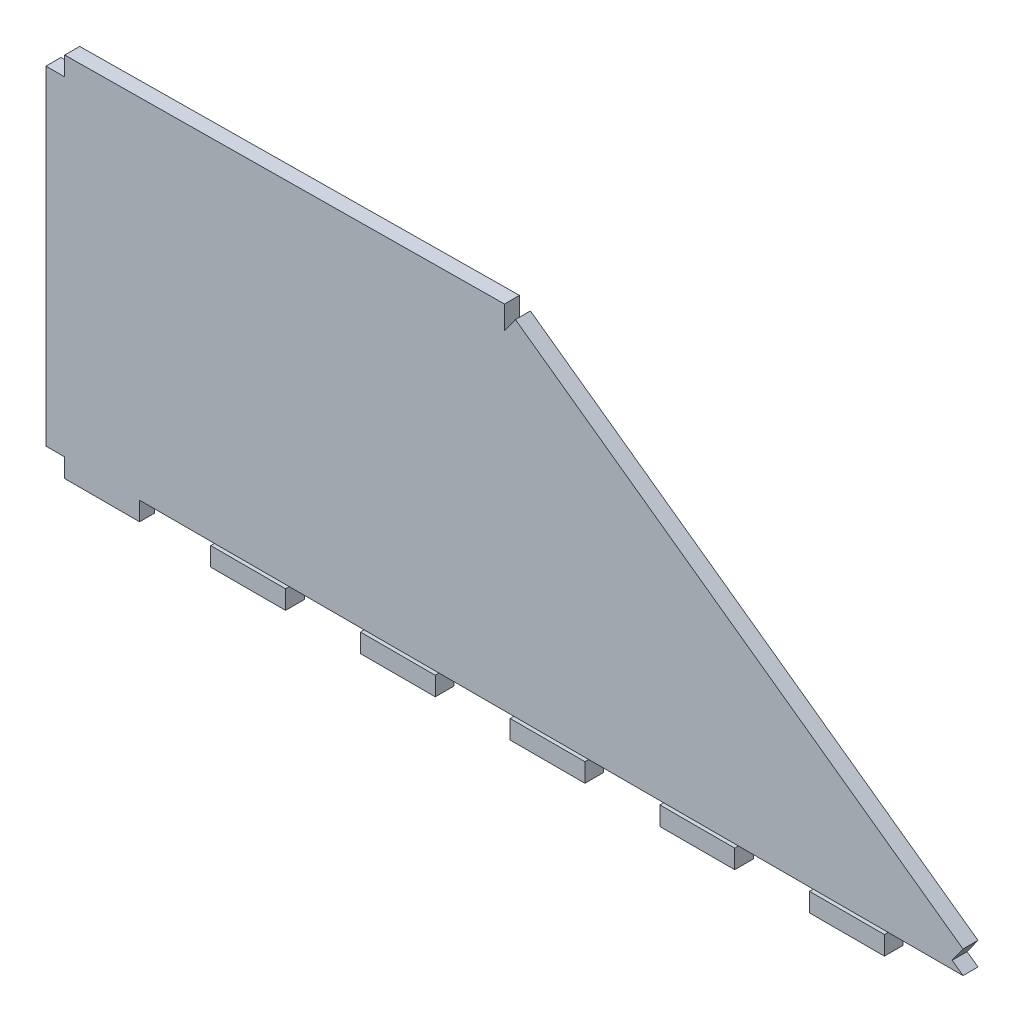
SolidWorks part; units mm, degrees
ref_plane "Front Plane" through (0, 0, 0) normal (0, 0, 1) x (1, 0, 0)
ref_plane "Top Plane" through (0, 0, 0) normal (0, 1, 0) x (1, 0, 0)
ref_plane "Right Plane" through (0, 0, 0) normal (1, 0, 0) x (0, 0, -1)
sketch "Sketch1" plane through (-5.3296, -16.203, 0) normal (0, 0, 1) x (1, 0, 0)
  line L0 (-139.4125, -47.2066) -> (-139.4125, -165.2411) construction
  line L1 (-294.9875, -47.2066) -> (-294.9875, -40.8566) construction
  line L2 (-294.9875, -47.2066) -> (-294.9875, -165.2411)
  line L3 (-294.9875, -165.2411) -> (16.1625, -165.2411) construction
  line L4 (16.1625, -158.8911) -> (16.1625, -165.2411)
  line L5 (-105.6158, -63.6519) -> (-109.3189, -68.8103) construction
  line L6 (-294.9875, -158.8911) -> (16.1625, -158.8911)
  line L7 (16.1625, -158.8911) -> (-139.4125, -47.2066)
  line L8 (-139.4125, -47.2066) -> (-294.9875, -47.2066)
  line L9 (16.1625, -158.8911) -> (16.1625, -151.0743) construction
  line L10 (-135.7094, -42.0482) -> (16.1625, -151.0743)
  line L11 (-139.4125, -47.2066) -> (-139.4125, -39.334)
  line L12 (-139.4125, -39.334) -> (-288.6375, -40.7811)
  line L13 (-288.6375, -165.2411) -> (-288.6375, -40.7811)
  line L14 (-139.4125, -47.2066) -> (-135.7094, -42.0482)
  line L15 (-139.4125, -39.334) -> (-135.7094, -42.0482) construction
  line L16 (16.1625, -151.0743) -> (12.4593, -156.2327)
  line L17 (-135.7094, -42.0482) -> (-139.4125, -39.334)
  line L18 (16.1625, -151.0743) -> (16.1625, -165.2411)
  line L19 (12.4593, -156.2327) -> (12.4593, -158.8911)
  line L21 (-288.6375, -165.2411) -> (-263.2375, -165.2411)
  line L22 (-288.6375, -165.2411) -> (-288.6375, -158.8911)
  line L23 (-288.6375, -158.8911) -> (-263.2375, -158.8911)
  line L24 (-263.2375, -165.2411) -> (-263.2375, -158.8911)
  line L25 (-237.8375, -158.8911) -> (-212.4375, -158.8911)
  line L26 (-237.8375, -158.8911) -> (-237.8375, -165.2411)
  line L27 (-237.8375, -165.2411) -> (-212.4375, -165.2411)
  line L28 (-212.4375, -158.8911) -> (-212.4375, -165.2411)
  line L29 (-187.0375, -158.8911) -> (-161.6375, -158.8911)
  line L30 (-187.0375, -158.8911) -> (-187.0375, -165.2411)
  line L31 (-187.0375, -165.2411) -> (-161.6375, -165.2411)
  line L32 (-161.6375, -158.8911) -> (-161.6375, -165.2411)
  line L33 (-136.2375, -158.8911) -> (-110.8375, -158.8911)
  line L34 (-136.2375, -158.8911) -> (-136.2375, -165.2411)
  line L35 (-136.2375, -165.2411) -> (-110.8375, -165.2411)
  line L36 (-110.8375, -158.8911) -> (-110.8375, -165.2411)
  line L37 (-85.4375, -158.8911) -> (-60.0375, -158.8911)
  line L38 (-85.4375, -158.8911) -> (-85.4375, -165.2411)
  line L39 (-85.4375, -165.2411) -> (-60.0375, -165.2411)
  line L40 (-60.0375, -158.8911) -> (-60.0375, -165.2411)
  line L41 (-34.6375, -158.8911) -> (-9.2375, -158.8911)
  line L42 (-34.6375, -158.8911) -> (-34.6375, -165.2411)
  line L43 (-34.6375, -165.2411) -> (-9.2375, -165.2411)
  line L44 (-9.2375, -158.8911) -> (-9.2375, -165.2411)
  point P32 (-161.6375, -162.0661)
  dimension "D1" = 6.35
  dimension "D2" = 311.15
  dimension "D3" = 6.35
  dimension "D4" = 6.35
  dimension "D5" = 6.35
  dimension "D6" = 124.46
  dimension "D7" = 25.4
  dimension "D8" = 25.4
  dimension "D9" = 25.4
  dimension "D10" = 25.4
  dimension "D11" = 25.4
  dimension "D12" = 25.4
  dimension "D13" = 25.4
  dimension "D14" = 25.4
  dimension "D15" = 25.4
  dimension "D16" = 25.4
  dimension "D17" = 25.4
extrude "Boss-Extrude1" add sketch "Sketch1" along normal blind 5.08 contours L16 L10 L14 L7 | L19 L7 L8 L13 L6 | L7 L19 L6 | L13 L3 L4 L6 | L6 L13 L8 L2 | L13 L8 L11 L12 region at (-297.1421, -119.2519, 0) region at (-216.8375, -59.8229, 0) region at (-176.0542, -125.6207, 0) region at (-281.2671, -178.2691, 0) region at (-66.9546, -115.3435, 0) region at (8.3641, -174.208, 0)
extrude "Boss-Extrude2" add sketch "Sketch1<4>" along normal blind 6.35 contours L28 L6 L26 L27 | L32 L6 L30 L31 | L36 L6 L34 L35 region at (-230.4671, -178.2691, 0) region at (-179.6671, -178.2691, 0) region at (-128.8671, -178.2691, 0)
sketch "Sketch1<4>" plane through (-5.3296, -16.203, 0) normal (0, 0, 1) x (1, 0, 0) same geometry as "Sketch1"
extrude "Boss-Extrude3" add sketch "Sketch1<5>" along normal blind 6.35 contours L40 L6 L38 L39 | L44 L6 L42 L43 region at (-27.2671, -178.2691, 0) region at (-78.0671, -178.2691, 0)
sketch "Sketch1<5>" plane through (-5.3296, -16.203, 0) normal (0, 0, 1) x (1, 0, 0) same geometry as "Sketch1"
